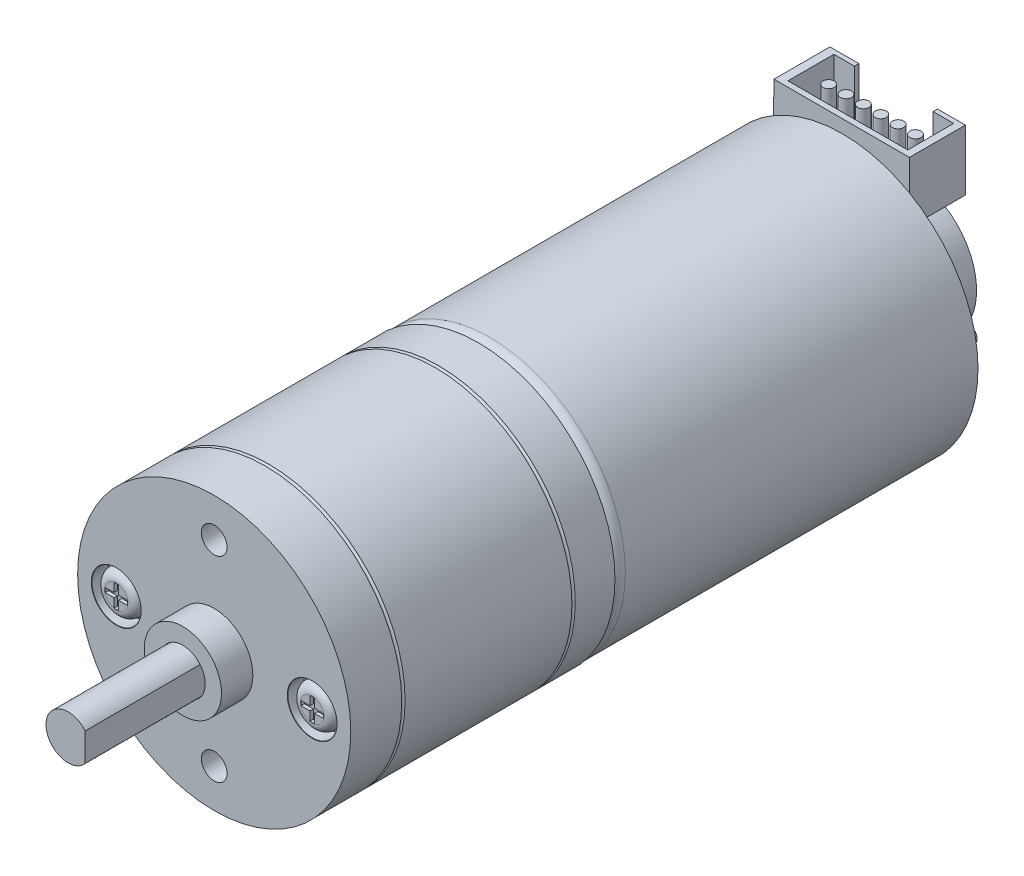
SolidWorks part; units mm, degrees
ref_plane "Front Plane" through (0, 0, 0) normal (0, 0, 1) x (1, 0, 0)
ref_plane "Top Plane" through (0, 0, 0) normal (0, 1, 0) x (1, 0, 0)
ref_plane "Right Plane" through (0, 0, 0) normal (1, 0, 0) x (0, 0, -1)
sketch "Sketch1" plane through (0, 0, 0) normal (0, 0, 1) x (1, 0, 0)
  circle A0 centre (0, 0) radius 12.125
  dimension "D1" = 24.25
extrude "Boss-Extrude1" add sketch "Sketch1" along normal blind 31
sketch "Sketch2" plane through (0, 0, 0) normal (0, 0, -1) x (-1, 0, 0)
  circle A1 centre (0, 0) radius 12.125
  circle A2 centre (0, 0) radius 12.125
  dimension "D1" = 0
fillet "Fillet2" radius 1 1 edges at (12.125, 0, 31)
shell "Shell1" thickness 1 removed face at (11.125, 0, 31)
ref_plane "Plane2" through (0, 0, 31) normal (0, 0, 1) x (1, 0, 0)
sketch "Sketch11" plane through (0, 0, 31) normal (0, 0, 1) x (1, 0, 0)
  circle A0 centre (0, 0) radius 12.2
  dimension "D1" = 24.4
extrude "Boss-Extrude4" add sketch "Sketch11" along normal blind 23.6 separate body
sketch "Sketch12" plane through (0, 0, 54.6) normal (0, 0, 1) x (1, 0, 0)
  circle A0 centre (0, 0) radius 3.45
  circle A1 centre (0, 0) radius 2
  dimension "D1" = 6.9
  dimension "D2" = 4
extrude "Boss-Extrude5" add sketch "Sketch12" along normal blind 2.8
sketch "Sketch14" plane through (0, 0, 54.6) normal (0, 0, 1) x (1, 0, 0)
  circle A0 centre (0, 0) radius 1.975
  dimension "D1" = 3.95
extrude "Boss-Extrude6" add sketch "Sketch14" along normal blind 13.05
sketch "Sketch16" plane through (0, 0, 67.65) normal (0, 0, 1) x (1, 0, 0)
  line L0 (-1.975, 0) -> (1.525, 0) construction
  line L1 (1.525, 0) -> (1.525, 1.255)
  line L2 (1.525, 0) -> (1.525, -1.255)
  circle A0 centre (0, 0) radius 1.975 construction
  arc A1 (1.525, -1.255) -> (1.525, 1.255) centre (0, 0) ccw
  dimension "D1" = 3.5
extrude "Cut-Extrude5" cut sketch "Sketch16" against normal up to surface (13.05 mm away) up to face at (3.45, 0, 54.6)
sketch "Sketch17" plane through (0, 0, 0) normal (0, 1, 0) x (1, 0, 0)
  line L0 (-12.2, -54.6) -> (-12.2, -49.9) construction
  line L1 (-12.2, -31) -> (-12.2, -54.6) construction
  line L2 (-12.2, -31) -> (-12.2, -34.7) construction
  circle A0 centre (-12.2, -49.9) radius 0.15
  circle A1 centre (-12.2, -34.7) radius 0.15
  dimension "D2" = 0.3
  dimension "D1" = 4.7
ref_axis "Axis1" through (0, 0, 54.6) along (0, 0, -1)
revolve "Cut-Revolve1" cut sketch "Sketch17" angle 360 about axis through (0, 0, 54.6) along (0, 0, -1)
sketch "Sketch18" plane through (0, 0, 54.6) normal (0, 0, 1) x (1, 0, 0)
  line L0 (0, 0) -> (8.75, 0) construction
  line L1 (0, 0) -> (0, 8.75) construction
  circle A1 centre (0, 8.75) radius 1.15
  circle A3 centre (0, -8.75) radius 1.15
  dimension "D3" = 2.3
extrude "Cut-Extrude7" cut sketch "Sketch18" against normal blind 10
sketch "Sketch19" plane through (0, 0, 0) normal (1, 0, 0) x (0, 0, -1)
  line L0 (-54.6, 9.9) -> (-53.4944, 10.0329)
  line L1 (-54.6, 9.9) -> (-54.6, 7.6) construction
  line L2 (-54.6, 12.2) -> (-54.6, -12.2) construction
  line L3 (-53.4944, 10.0329) -> (-53.399, 9.9)
  line L4 (-53.399, 9.9) -> (-54.6, 9.9)
sketch "Sketch20" plane through (0, 0, 54.6) normal (0, 0, 1) x (1, 0, 0)
  circle A0 centre (0, 8.75) radius 1.1448
curve "Helix/Spiral1" pitch 0.5 height 6 turns 12
sketch "Sketch21" plane through (0, 0, 54.6) normal (0, 0, 1) x (1, 0, 0)
  line L0 (0, 0) -> (0, -5.9622) construction
  circle A1 centre (8.75, 0) radius 2.25
  circle A2 centre (-8.75, 0) radius 2.25
  dimension "D1" = 4.5
hole_wizard "CBORE for M2 Cheese Head Screw1" positions "3DSketch1" profile "Sketch23" counterbore size "M2" standard "DIN"
sketch3d "3DSketch1"
  point P0 (-8.75, 0, 54.6)
  point P3 (8.75, 0, 54.6)
sketch "Sketch23" plane through (-8.75, 0, 54.6) normal (1, 0, 0) x (0, -1, 0)
  line L0 (0, 0) -> (0, 5.7811)
  line L1 (0, 5.7811) -> (1.3, 5)
  line L2 (1.3, 5) -> (1.3, 1.4)
  line L3 (1.3, 1.4) -> (2.2, 1.4)
  line L5 (2.2, 1.4) -> (2.2, 0.025)
  line L6 (2.2, 0.025) -> (2.225, 0)
  line L7 (2.225, 0) -> (0, 0)
  line L8 (-2.2, 0.025) -> (-2.225, 0) construction
  line L10 (0, 5.7811) -> (-1.3, 5) construction
  line L11 (0, -6.35) -> (0, 107.95) construction
  dimension "Hole Dia." = 2.6
  dimension "Hole Depth" = 5
  dimension "C'Bore Dia." = 4.4
  dimension "C'Bore Depth" = 1.4
  dimension "Near C'Sink Dia." = 4.45
  dimension "Near C'Sink Angle" = 90
  dimension "Drill Angle" = 118
sketch "Sketch24" plane through (0, 0, 53.2) normal (0, 0, 1) x (1, 0, 0)
  circle A0 centre (-8.75, 0) radius 1.8422
extrude "Boss-Extrude7" add sketch "Sketch24" along normal blind 1.4
sketch "Sketch25" plane through (0, 0, 54.6) normal (0, 0, 1) x (1, 0, 0)
  line L0 (-8.55, 0.2) -> (-7.75, 0.2)
  line L1 (-9.75, 0.2) -> (-8.95, 0.2)
  line L2 (-9.75, 0.2) -> (-9.75, -0.2)
  line L3 (-9.75, -0.2) -> (-8.95, -0.2)
  line L4 (-7.75, 0.2) -> (-7.75, -0.2)
  line L7 (-8.95, 1) -> (-8.55, 1)
  line L8 (-8.95, 1) -> (-8.95, 0.2)
  line L9 (-8.95, -1) -> (-8.55, -1)
  line L10 (-8.55, 1) -> (-8.55, 0.2)
  line L12 (-8.55, -0.2) -> (-7.75, -0.2)
  line L13 (-8.95, -0.2) -> (-8.95, -1)
  line L16 (-8.55, -0.2) -> (-8.55, -1)
  point P0 (-8.75, 0)
  point P5 (-8.75, 0)
extrude "Cut-Extrude9" cut sketch "Sketch25" against normal blind 0.3
fillet "Fillet3" radius 0.8 1 edges at (-6.9078, 0, 54.6)
mirror "Mirror2" about plane through (0, 0, 0) normal (1, 0, 0) of "Fillet3", "Cut-Extrude9", "Boss-Extrude7"
ref_plane "Plane3" through (0, 0, 0) normal (0, 0, -1) x (-1, 0, 0)
sketch "Sketch26" plane through (0, 0, 0) normal (0, 0, -1) x (-1, 0, 0)
  circle A0 centre (0, 0) radius 12.125
extrude "Boss-Extrude8" add sketch "Sketch26" along normal blind 1.5
ref_plane "Plane4" through (0, 0, -1.5) normal (0, 0, -1) x (-1, 0, 0)
sketch "Sketch27" plane through (0, 0, -1.5) normal (0, 0, -1) x (-1, 0, 0)
  circle A0 centre (0, 0) radius 6
  dimension "D1" = 12
extrude "Boss-Extrude9" add sketch "Sketch27" along normal blind 5 from offset 1 separate body contours A0
sketch "Sketch28" plane through (0, 0, -1.5) normal (0, 0, -1) x (-1, 0, 0)
  circle A0 centre (0, 0) radius 0.75
extrude "Boss-Extrude10" add sketch "Sketch28" along normal blind 8 contours A0
sketch "Sketch29" plane through (0, 0, -1.5) normal (0, 0, -1) x (-1, 0, 0)
  line L1 (6.0994, 13.2874) -> (-6, 13.2874)
  line L2 (6.0994, 13.2874) -> (6.1786, 7.872)
  line L3 (6.1786, 7.872) -> (-6, 7.872)
  line L4 (-6, 13.2874) -> (-6, 7.872)
  line L5 (6.0994, 13.2874) -> (-6, 7.872) construction
  line L6 (6.1786, 7.872) -> (-6, 13.2874) construction
  point P0 (0, 10.0459)
extrude "Boss-Extrude11" add sketch "Sketch29" along normal blind 5
ref_plane "Plane5" through (0, 13.2874, 0) normal (0, 1, 0) x (1, 0, 0)
sketch "Sketch31" plane through (0, 13.2874, 0) normal (0, 1, 0) x (1, 0, 0)
  line L1 (5.3489, 6.1016) -> (-5.3489, 6.1016)
  line L2 (5.3489, 6.1016) -> (5.3489, 1.9988)
  line L3 (5.3489, 1.9988) -> (-5.3489, 1.9988)
  line L4 (-5.3489, 6.1016) -> (-5.3489, 1.9988)
  line L5 (5.3489, 6.1016) -> (-5.3489, 1.9988) construction
  line L6 (5.3489, 1.9988) -> (-5.3489, 6.1016) construction
  line L7 (3.5118, 10.53) -> (-3.5118, 10.53)
  line L8 (3.5118, 10.53) -> (3.5118, 3.7483)
  line L9 (3.5118, 3.7483) -> (-3.5118, 3.7483)
  line L10 (-3.5118, 10.53) -> (-3.5118, 3.7483)
  line L11 (3.5118, 10.53) -> (-3.5118, 3.7483) construction
  line L12 (3.5118, 3.7483) -> (-3.5118, 10.53) construction
  point P0 (0, 4.0502)
  point P5 (0, 7.1391)
  line M3 (6, 6.5) -> (-6.0994, 6.5)
extrude "Cut-Extrude10" cut sketch "Sketch31" against normal blind 4.5 contours L10 L1 L4 L3 L2 L8 L9 | L1 L10 L9 L8 | L10 L1 L8 M3 region at (0, 13.2874, -3.5218) region at (0, 13.2874, -4.9249) region at (0, 13.2874, -6.3008)
sketch "Sketch32" plane through (0, 8.7874, 0) normal (0, 1, 0) x (1, 0, 0)
  circle A0 centre (3.9803, 4.0556) radius 0.5
  circle A1 centre (2.4303, 4.0556) radius 0.5
  circle A2 centre (0.8803, 4.0556) radius 0.5
  circle A3 centre (-0.6697, 4.0556) radius 0.5
  circle A4 centre (-2.2197, 4.0556) radius 0.5
  circle A5 centre (-3.7697, 4.0556) radius 0.5
  dimension "D1" = 6
extrude "Boss-Extrude12" add sketch "Sketch32" along normal blind 4 contours A0 | A1 | A2 | A3 | A4 | A5
sketch "Sketch33" plane through (0, 0, -1.5) normal (0, 0, -1) x (-1, 0, 0)
  line L0 (5.822, -4.3383) -> (7.2246, -1.6864) construction
  line L1 (5.159, -3.9877) -> (6.5616, -1.3357)
  line L2 (6.485, -4.6889) -> (7.8876, -2.037)
  line L3 (-5.736, -4.291) -> (-7.2951, -1.7279) construction
  line L4 (-6.3768, -4.6808) -> (-7.9358, -2.1177)
  line L5 (-5.0952, -3.9012) -> (-6.6543, -1.3382)
  line L6 (0, 0) -> (0, -6.9518) construction
  line L7 (-8.5109, 0.5462) -> (-10.6566, 0.5462)
  line L8 (-8.5109, 0.5462) -> (-8.5109, -0.5462)
  line L9 (-8.5109, -0.5462) -> (-10.6566, -0.5462)
  line L10 (-10.6566, 0.5462) -> (-10.6566, -0.5462)
  line L11 (-8.5109, 0.5462) -> (-10.6566, -0.5462) construction
  line L12 (-8.5109, -0.5462) -> (-10.6566, 0.5462) construction
  line L13 (10.6566, 0.5462) -> (10.6566, -0.5462)
  line L14 (8.5109, -0.5462) -> (10.6566, -0.5462)
  line L15 (8.5109, 0.5462) -> (8.5109, -0.5462)
  line L16 (8.5109, 0.5462) -> (10.6566, 0.5462)
  line L17 (2.5787, -9.2868) -> (1.7583, -9.2868)
  line L18 (-2.5787, -7.2673) -> (-1.7583, -7.2673)
  line L19 (-2.5787, -7.2673) -> (-2.5787, -9.2868)
  line L20 (-2.5787, -9.2868) -> (-1.7583, -9.2868)
  line L21 (-1.7583, -7.2673) -> (-1.7583, -9.2868)
  line L22 (-2.5787, -7.2673) -> (-1.7583, -9.2868) construction
  line L23 (-2.5787, -9.2868) -> (-1.7583, -7.2673) construction
  line L24 (2.5787, -7.2673) -> (2.5787, -9.2868)
  line L25 (1.7583, -7.2673) -> (1.7583, -9.2868)
  line L26 (2.5787, -7.2673) -> (1.7583, -7.2673)
  arc A0 (5.159, -3.9877) -> (6.485, -4.6889) centre (5.822, -4.3383) ccw
  arc A1 (7.8876, -2.037) -> (6.5616, -1.3357) centre (7.2246, -1.6864) ccw
  arc A2 (-6.3768, -4.6808) -> (-5.0952, -3.9012) centre (-5.736, -4.291) ccw
  arc A3 (-6.6543, -1.3382) -> (-7.9358, -2.1177) centre (-7.2951, -1.7279) ccw
  point P2 (6.5233, -3.0123)
  point P7 (-6.5155, -3.0095)
  point P19 (-9.5838, 0)
  point P26 (-2.1685, -8.2771)
extrude "Boss-Extrude13" add sketch "Sketch33" along normal blind 4 contours L2 A1 L1 A0 | A3 L4 A2 L5 region at (-6.5233, -3.0123, -1.5)
extrude "Boss-Extrude14" add sketch "Sketch33<4>" along normal blind 1
sketch "Sketch33<4>" plane through (0, 0, -1.5) normal (0, 0, -1) x (-1, 0, 0) same geometry as "Sketch33"
